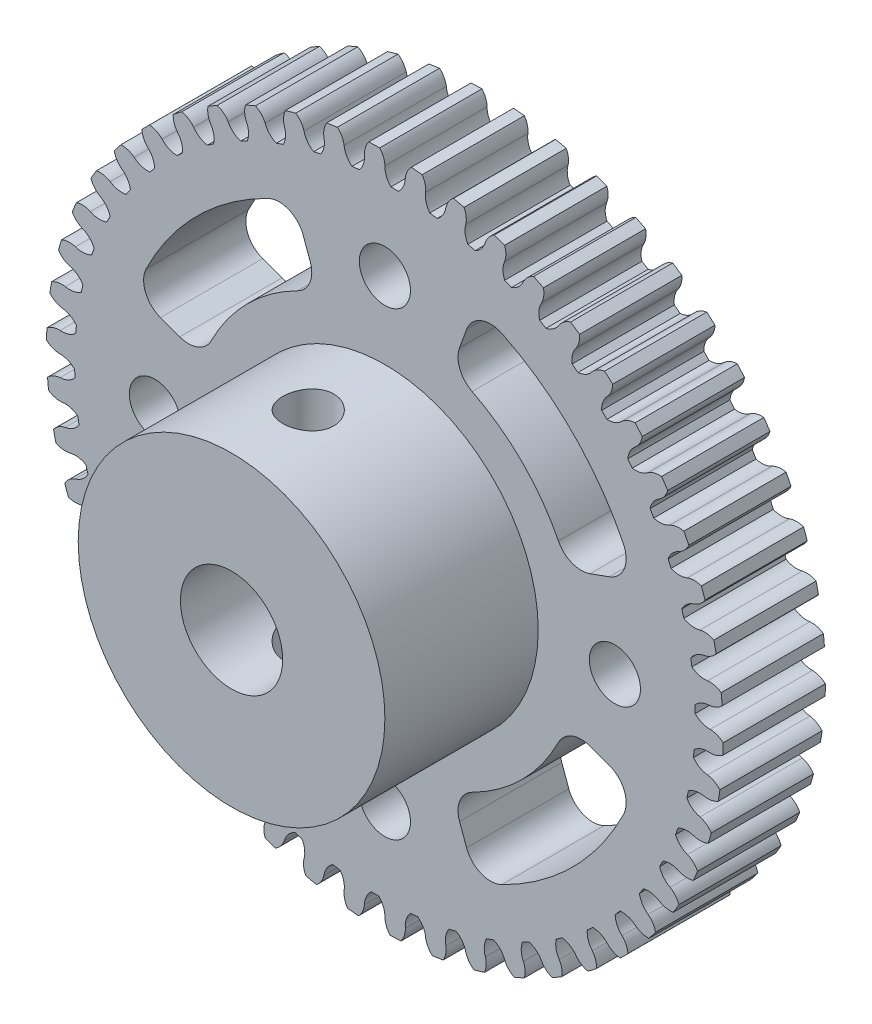
SolidWorks part; units mm, degrees
ref_plane "Front Plane" through (0, 0, 0) normal (0, 0, 1) x (1, 0, 0)
ref_plane "Top Plane" through (0, 0, 0) normal (0, 1, 0) x (1, 0, 0)
ref_plane "Right Plane" through (0, 0, 0) normal (1, 0, 0) x (0, 0, -1)
sketch "Sketch1" plane through (0, 0, 0) normal (0, 0, 1) x (1, 0, 0)
  circle A0 centre (0, 0) radius 33.1
  dimension "D1" = 66.2
extrude "Boss-Extrude2" add sketch "Sketch1" along normal blind 10
sketch "Sketch3" plane through (0, 0, 10) normal (0, 0, 1) x (1, 0, 0)
  arc A0 (3.3067, 33.2805) -> (-0.8914, 33.4324) centre (0, 0) ccw
  arc A2 (0, 31.83) -> (0.5936, 30.3442) centre (1.999, 31.7672) ccw
  arc A3 (1.3133, 30.3216) -> (1.999, 31.7672) centre (0, 31.83) ccw
  arc A4 (3.3067, 33.2805) -> (3.1576, 33.3974) centre (1.999, 31.7672) ccw
  arc A6 (3.1576, 33.3974) -> (1.999, 31.7672) centre (3.9901, 31.5789) ccw
  arc A7 (0, 31.83) -> (-0.8914, 33.4324) centre (-1.999, 31.7672) ccw
  arc A8 (1.3133, 30.3216) -> (0.5936, 30.3442) centre (0, 0) ccw
  circle M1 centre (0, 0) radius 33.1
extrude "Cut-Extrude1" cut sketch "Sketch3" against normal blind 18 contours A8 A3 A6 A7 A2 M1 region at (1.0029, 31.9055, 10)
pattern_circular "CirPattern1" count 50 over 360 about axis through (0, 0, 10) along (0, 0, 1) of "Cut-Extrude1"
sketch "Sketch4" plane through (0, 0, 0) normal (0, 0, -1) x (-1, 0, 0)
  circle A0 centre (0, 0) radius 5
extrude "Cut-Extrude2" cut sketch "Sketch4" against normal blind 78
sketch "Sketch5" plane through (0, 0, 10) normal (0, 0, 1) x (1, 0, 0)
  circle A0 centre (0, 0) radius 5
  circle A1 centre (0, 0) radius 15
extrude "Boss-Extrude3" add sketch "Sketch5" along normal blind 15
sketch "Sketch8" plane through (0, 0, 10) normal (0, 0, 1) x (1, 0, 0)
  line L0 (0, 0) -> (-22.5, 0) construction
  circle A0 centre (-22.5, 0) radius 2.5
  circle A1 centre (0, 22.5) radius 2.5
  circle A2 centre (22.5, 0) radius 2.5
  circle A3 centre (0, -22.5) radius 2.5
  point P13 (0, 0)
  dimension "D1" = 4
extrude "Cut-Extrude3" cut sketch "Sketch8" against normal blind 40
sketch "Sketch9" plane through (0, 0, 10) normal (0, 0, 1) x (1, 0, 0)
  circle A0 centre (0, 0) radius 30.35
sketch "Sketch11" plane through (0, 0, 0) normal (0, 1, 0) x (1, 0, 0)
  line L0 (0, -25) -> (0, -17.5) construction
  line L1 (-15, -25) -> (15, -25) construction
  circle A0 centre (0, -17.5) radius 2.5
extrude "Cut-Extrude4" cut sketch "Sketch11" along normal blind 70 and the other way blind 107
sketch "Sketch13" plane through (0, 0, 10) normal (0, 0, 1) x (1, 0, 0)
  line L0 (-7.3036, 20.0663) -> (-7.9919, 21.9575)
  line L1 (-20.0663, 7.3036) -> (-21.9575, 7.9919)
  line L2 (0, 0) -> (0, 51.1275) construction
  line L3 (20.0663, 7.3036) -> (21.9575, 7.9919)
  line L4 (7.3036, 20.0663) -> (7.9919, 21.9575)
  line L5 (7.3036, -20.0663) -> (7.9919, -21.9575)
  line L6 (20.0663, -7.3036) -> (21.9575, -7.9919)
  line L7 (-20.0663, -7.3036) -> (-21.9575, -7.9919)
  line L8 (-7.3036, -20.0663) -> (-7.9919, -21.9575)
  arc A0 (-11.4412, 23.3473) -> (-23.3473, 11.4412) centre (0, 0) ccw
  arc A1 (-8.5304, 16.9774) -> (-16.9774, 8.5304) centre (0, 0) ccw
  arc A2 (-20.0663, 7.3036) -> (-16.9774, 8.5304) centre (-19.2113, 9.6528) ccw
  arc A3 (-23.3473, 11.4412) -> (-21.9575, 7.9919) centre (-21.1024, 10.3411) ccw
  arc A4 (-8.5304, 16.9774) -> (-7.3036, 20.0663) centre (-9.6528, 19.2113) ccw
  arc A5 (-11.4412, 23.3473) -> (-7.9919, 21.9575) centre (-10.3411, 21.1024) cw
  arc A6 (16.9774, 8.5304) -> (8.5304, 16.9774) centre (0, 0) ccw
  arc A7 (16.9774, 8.5304) -> (20.0663, 7.3036) centre (19.2113, 9.6528) ccw
  arc A8 (23.3473, 11.4412) -> (21.9575, 7.9919) centre (21.1024, 10.3411) cw
  arc A9 (23.3473, 11.4412) -> (11.4412, 23.3473) centre (0, 0) ccw
  arc A10 (11.4412, 23.3473) -> (7.9919, 21.9575) centre (10.3411, 21.1024) ccw
  arc A11 (7.3036, 20.0663) -> (8.5304, 16.9774) centre (9.6528, 19.2113) ccw
  arc A12 (8.5304, -16.9774) -> (16.9774, -8.5304) centre (0, 0) ccw
  arc A13 (8.5304, -16.9774) -> (7.3036, -20.0663) centre (9.6528, -19.2113) ccw
  arc A14 (11.4412, -23.3473) -> (7.9919, -21.9575) centre (10.3411, -21.1024) cw
  arc A15 (11.4412, -23.3473) -> (23.3473, -11.4412) centre (0, 0) ccw
  arc A16 (23.3473, -11.4412) -> (21.9575, -7.9919) centre (21.1024, -10.3411) ccw
  arc A17 (20.0663, -7.3036) -> (16.9774, -8.5304) centre (19.2113, -9.6528) ccw
  arc A18 (-16.9774, -8.5304) -> (-8.5304, -16.9774) centre (0, 0) ccw
  arc A19 (-16.9774, -8.5304) -> (-20.0663, -7.3036) centre (-19.2113, -9.6528) ccw
  arc A20 (-23.3473, -11.4412) -> (-21.9575, -7.9919) centre (-21.1024, -10.3411) cw
  arc A21 (-23.3473, -11.4412) -> (-11.4412, -23.3473) centre (0, 0) ccw
  arc A22 (-11.4412, -23.3473) -> (-7.9919, -21.9575) centre (-10.3411, -21.1024) ccw
  arc A23 (-7.3036, -20.0663) -> (-8.5304, -16.9774) centre (-9.6528, -19.2113) ccw
  point P54 (0, 0)
  dimension "D1" = 20
  dimension "D3" = 2.5
  dimension "D2" = 70
  dimension "D4" = 4
extrude "Cut-Extrude5" cut sketch "Sketch13" against normal blind 87
